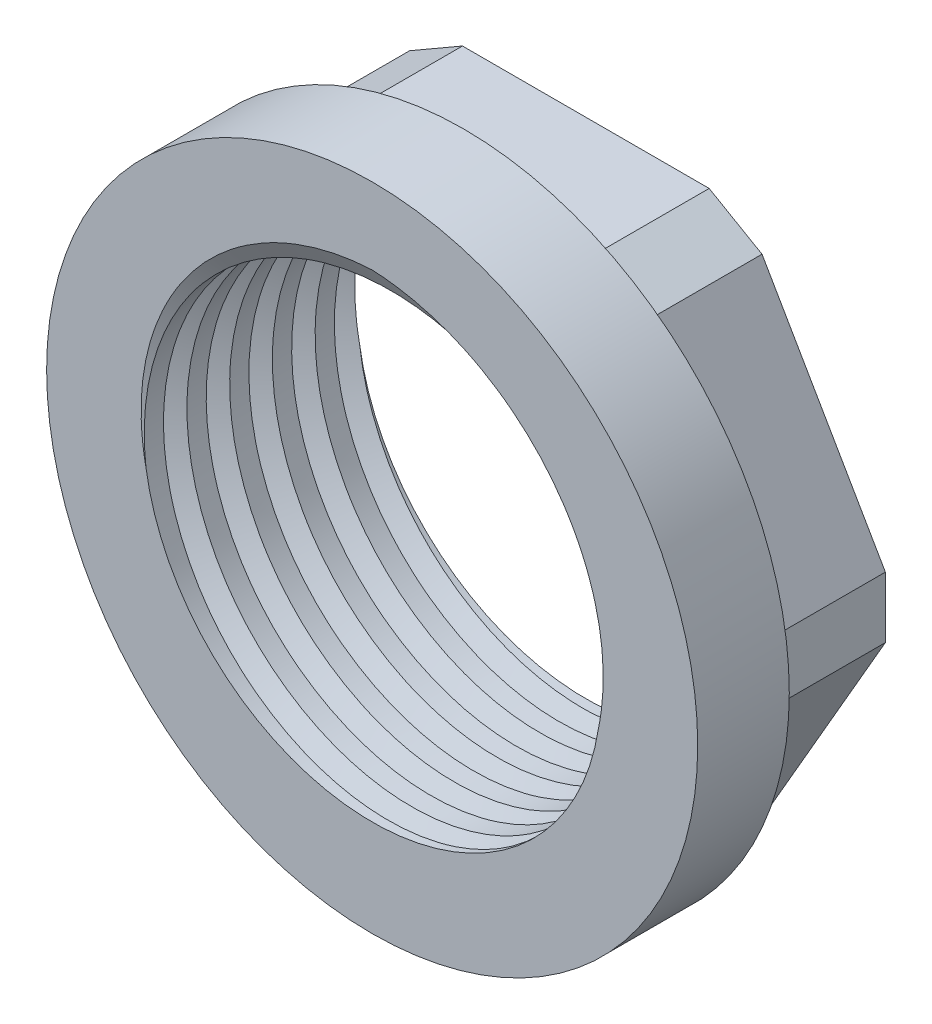
SolidWorks part; units mm, degrees
ref_plane "Alzado" through (0, 0, 0) normal (0, 0, 1) x (1, 0, 0)
ref_plane "Planta" through (0, 0, 0) normal (0, 1, 0) x (1, 0, 0)
ref_plane "Vista lateral" through (0, 0, 0) normal (1, 0, 0) x (0, 0, -1)
sketch "Croquis1" plane through (0, 0, 0) normal (0, 0, 1) x (1, 0, 0)
  line L1 (7.7942, 13.5) -> (-7.7942, 13.5)
  line L2 (-7.7942, 13.5) -> (-15.5885, 0)
  line L3 (-15.5885, 0) -> (-7.7942, -13.5)
  line L4 (-7.7942, -13.5) -> (7.7942, -13.5)
  line L5 (7.7942, -13.5) -> (15.5885, 0)
  line L6 (15.5885, 0) -> (7.7942, 13.5)
  circle A0 centre (0, 0) radius 13.5 construction
  point P1 (0, 0)
  dimension "D1" = 27
extrude "Saliente-Extruir1" add sketch "Croquis1" along normal blind 6
fillet "Chaflán1" radius 3 1 edges at (7.7942, 13.5, 3) profile chamfer
fillet "Chaflán2" radius 3 5 edges at (-15.5885, 0, 3) (-7.7942, -13.5, 3) (7.7942, -13.5, 3) (15.5885, 0, 3) (-7.7942, 13.5, 3) profile chamfer
sketch "Croquis2" plane through (0, 0, 6) normal (0, 0, 1) x (1, 0, 0)
  circle A0 centre (0, 0) radius 16
  dimension "D1" = 32
extrude "Saliente-Extruir2" add sketch "Croquis2" along normal blind 4.5
sketch "Croquis3" plane through (0, 0, 0) normal (0, 0, -1) x (-1, 0, 0)
  circle A0 centre (0, 0) radius 11.25
  dimension "D1" = 22.5
extrude "Cortar-Extruir1" cut sketch "Croquis3" against normal blind 34.5
sketch "Croquis4" plane through (0, 0, 0) normal (1, 0, 0) x (0, 0, -1)
  line L0 (-10.5, 11.25) -> (-10.5, -11.25) construction
  line L1 (-10.5, 11.25) -> (-10.5, -11.25)
  line L3 (-10.5, 12.25) -> (-11.366, 10.75)
  line L4 (-11.366, 10.75) -> (-9.634, 10.75)
  line L5 (-9.634, 10.75) -> (-10.5, 12.25)
  circle A0 centre (-10.5, 11.25) radius 0.5 construction
  point P2 (0, 0)
  dimension "D1" = 1
sketch "Croquis5" plane through (0, 0, 10.5) normal (0, 0, 1) x (1, 0, 0)
  circle A0 centre (0, 0) radius 11.25 construction
  circle A1 centre (0, 0) radius 11.25
curve "Hélice/Espiral1" pitch 2.1 height 10.5 radius 11.25 centre (0, 0, 10.5) axis (0, 0, -1) start towards (0, 1, 0)
sweep "Cortar-Barrer1" cut profiles "Croquis4" path "Hélice/Espiral1" align with end faces yes
